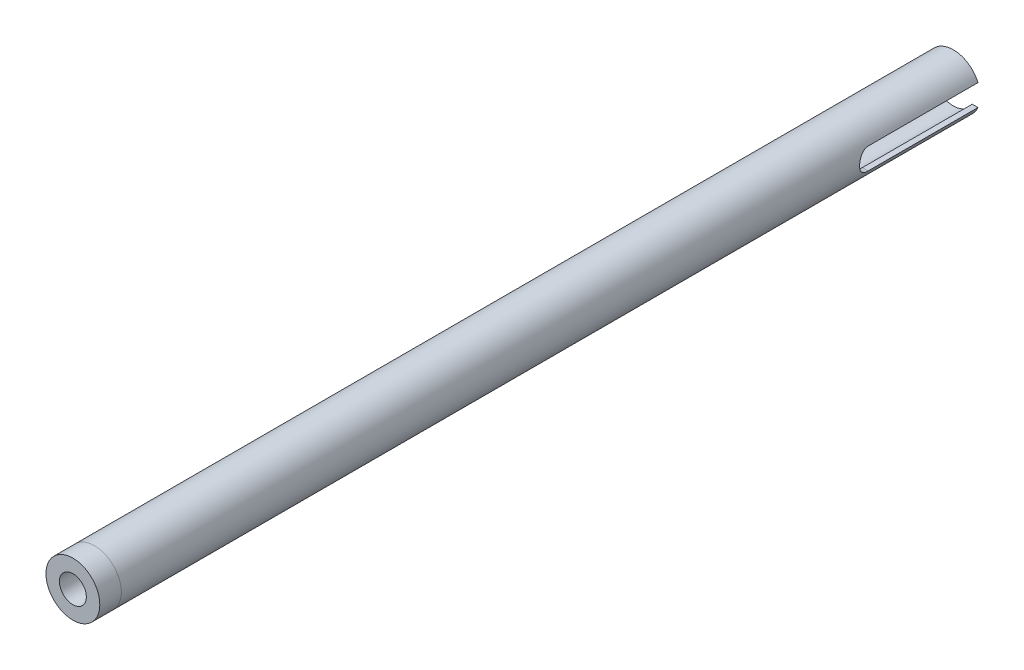
SolidWorks part; units mm, degrees
material "AISI 4130 Steel, annealed at 865C"
ref_plane "Front Plane" through (0, 0, 0) normal (0, 0, 1) x (1, 0, 0)
ref_plane "Top Plane" through (0, 0, 0) normal (0, 1, 0) x (1, 0, 0)
ref_plane "Right Plane" through (0, 0, 0) normal (1, 0, 0) x (0, 0, -1)
sketch "Axis" plane through (0, 0, 0) normal (0, 1, 0) x (1, 0, 0)
  line L0 (0, 0) -> (0, 259.5593) construction
  line L1 (0, 0) -> (0, -34.925) construction
  line L2 (0, 259.5593) -> (-7.9375, 259.5593) construction
  line L3 (0, 282.9826) -> (-10.3188, 252.5323) construction
  dimension "D1" = 34.925
  dimension "D2" = 7.9375
sketch "Sketch1" plane through (0, 0, 0) normal (0, 0, 1) x (1, 0, 0)
  line L0 (-7.9375, 0) -> (7.9375, 0) construction
  line L1 (-7.2748, 3.175) -> (7.2748, 3.175)
  line L2 (-7.2748, -3.175) -> (7.2748, -3.175)
  circle A0 centre (0, 0) radius 7.9375
  circle A1 centre (0, 0) radius 6.4135
  circle A2 centre (0, 0) radius 3.9688
  dimension "D1" = 15.875
  dimension "D3" = 7.9375
  dimension "D2" = 1.524
  dimension "D4" = 6.35
extrude "Threaded insert 1-1" add sketch "Sketch1" against normal blind 6.35 contours A2 L1 A1 | A1 L1 A0 | A2 L0 A1 L1 | A1 L0 A0 L1 | L0 A1 L2 A0 | L0 A2 L2 A1 | A2 L2 A1 | A1 L2 A0 | L0 A1 L2 A2 | L0 A0 L2 A1 | A0 L0 A1 L1 | A1 L0 A2 L1 region at (4.7887, 1.6543, 0) region at (4.7887, -1.6543, 0) region at (6.9234, 1.6163, 0) region at (6.9234, -1.6163, 0) region at (-4.7887, -1.6543, 0) region at (-4.7887, 1.6543, 0) region at (0, 4.6159, 0) region at (0, -4.6159, 0) region at (0, 6.5666, 0) region at (6.4237, -3.3281, 0) region at (-6.9234, -1.6163, 0) region at (-6.9234, 1.6163, 0)
extrude "Threaded insert 1-2" add sketch "Sketch1<3>" against normal blind 9.525 from surface contours A2 L1 A1 | A2 L0 A1 L1 | L0 A2 L2 A1 | A2 L2 A1 | L0 A1 L2 A2 | A1 L0 A2 L1 region at (4.7887, 1.6543, 0) region at (4.7887, -1.6543, 0) region at (-4.7887, -1.6543, 0) region at (-4.7887, 1.6543, 0) region at (0, 4.6159, 0) region at (0, -4.6159, 0) starting at face at (7.9375, 0, -6.35)
sketch "Sketch1<3>" plane through (0, 0, 0) normal (0, 0, 1) x (1, 0, 0) same geometry as "Sketch1"
extrude "A-arm tube" add sketch "Sketch1<4>" against normal up to vertex (259.5593 mm away) from surface separate body contours A1 L1 A0 | A1 L0 A0 L1 | L0 A1 L2 A0 | A1 L2 A0 | L0 A0 L2 A1 | A0 L0 A1 L1 region at (6.9234, 1.6163, 0) region at (6.9234, -1.6163, 0) region at (0, 6.5666, 0) region at (6.4237, -3.3281, 0) region at (-6.9234, -1.6163, 0) region at (-6.9234, 1.6163, 0) up to point (0, 0, -259.5593) starting at face at (6.4135, 0, -6.35)
sketch "Sketch1<4>" plane through (0, 0, 0) normal (0, 0, 1) x (1, 0, 0) same geometry as "Sketch1"
extrude "Apex slot" cut sketch "Sketch1<5>" along normal blind 35.56 from surface contours A0 L0 A1 L1 | L0 A0 L2 A1 | A1 L0 A0 L1 | L0 A1 L2 A0 region at (6.9234, 1.6163, 0) region at (6.9234, -1.6163, 0) region at (-6.9234, -1.6163, 0) region at (-6.9234, 1.6163, 0) starting at face at (6.4135, 0, -259.5593)
sketch "Sketch1<5>" plane through (0, 0, 0) normal (0, 0, 1) x (1, 0, 0) same geometry as "Sketch1"
fillet "Fillet1" radius 3.175 4 edges at (-6.4237, 3.175, -223.9993) (-6.4237, -3.175, -223.9993) (6.4237, -3.175, -223.9993) (6.4237, 3.175, -223.9993)
equation "\"tube diameter\"= 5 / 8"
equation "\"tube thickness\"= .06"
equation "\"apex thickness\"= .25"
equation "\"tube slot\"= 1.4"
equation "\"D1@Sketch1\"=\"tube diameter\""
equation "\"D2@Sketch1\"=\"tube thickness\""
equation "\"threaded insert hole\"= .3125"
equation "\"D3@Sketch1\"=\"threaded insert hole\""
equation "\"D4@Sketch1\"=\"apex thickness\""
equation "\"D1@Apex slot\" = \"tube slot\""
equation "\"D1@Fillet1\"=\"apex thickness\"/2"
